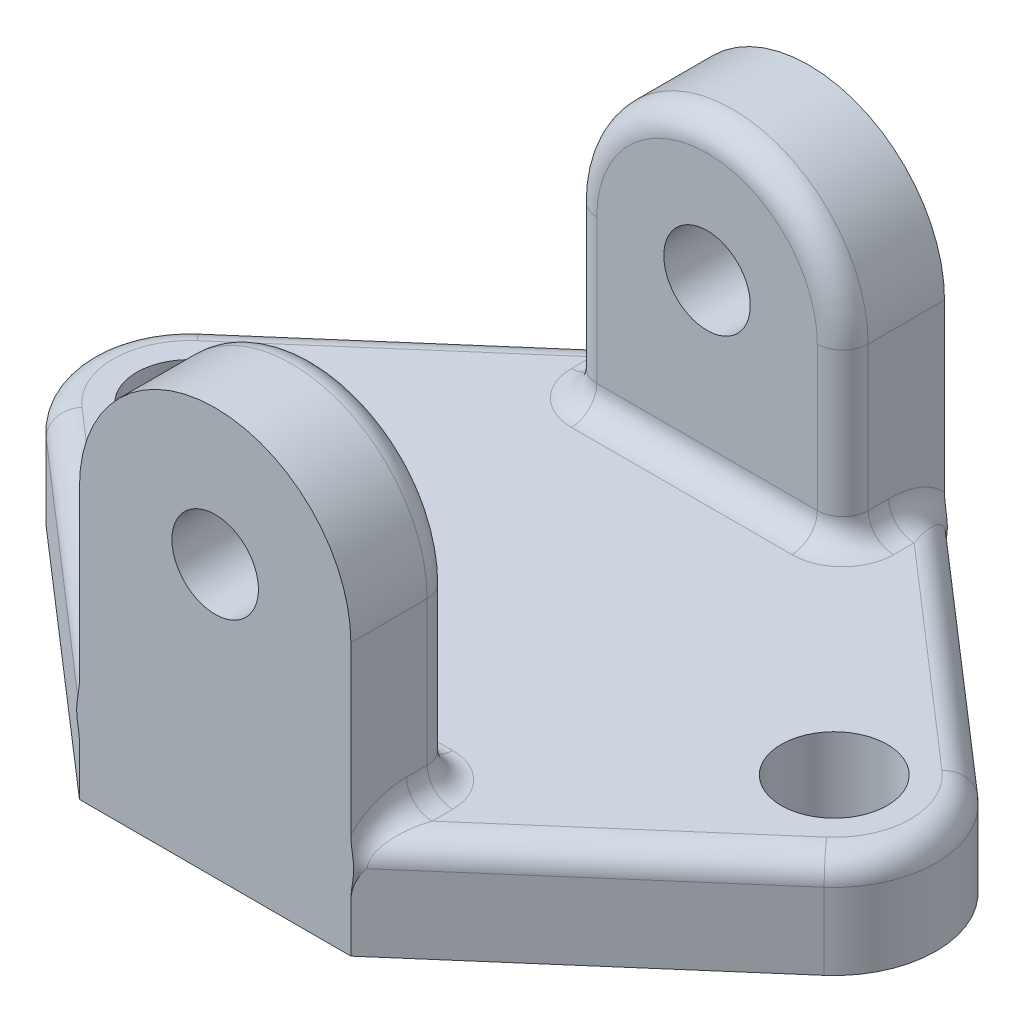
SolidWorks part; units mm, degrees
material "Plain Carbon Steel"
ref_plane "Front" through (0, 0, 0) normal (0, 0, 1) x (1, 0, 0)
ref_plane "Top" through (0, 0, 0) normal (0, 1, 0) x (1, 0, 0)
ref_plane "Right" through (0, 0, 0) normal (1, 0, 0) x (0, 0, -1)
sketch "Sketch1" plane through (0, 0, 0) normal (0, 1, 0) x (1, 0, 0)
  line L0 (0, 44.7996) -> (0, -49.8042) construction
  line L1 (-62.4772, 0) -> (76.0382, 0) construction
  line L2 (-16, 35) -> (16, 35)
  line L3 (16, 35) -> (45.8685, 9.0602)
  line L4 (-16, 35) -> (-45.8685, 9.0602)
  line L5 (50, 0) -> (-50, 0)
  arc A0 (45.8685, 9.0602) -> (50, 0) centre (38, 0) cw
  arc A1 (-45.8685, 9.0602) -> (-50, 0) centre (-38, 0) ccw
  point P8 (0, 35)
  point P12 (0, 0)
  dimension "D3" = 12
  dimension "D4" = 70
  dimension "D1" = 32
  dimension "D2" = 76
extrude "Boss-Extrude1" add sketch "Sketch1" along normal blind 12
sketch "Sketch2" plane through (0, 0, -35) normal (0, 0, -1) x (-1, 0, 0)
  line L0 (-16, 12) -> (-16, 32)
  line L1 (-16, 12) -> (16, 12)
  line L2 (16, 12) -> (16, 32)
  arc A0 (16, 32) -> (-16, 32) centre (0, 32) ccw
  dimension "D1" = 32
extrude "Boss-Extrude2" add sketch "Sketch2" against normal blind 12
hole_wizard "M12x1.75 Tapped Hole1" positions "Sketch4" profile "Sketch5" tap size "M12x1.75" standard "ANSI Metric" end condition up to next
sketch "Sketch4" plane through (0, 0, -35) normal (0, 0, -1) x (-1, 0, 0)
  point P0 (0, 32)
sketch "Sketch5" plane through (0, 32, -35) normal (1, 0, 0) x (0, 1, 0)
  line L0 (0, 0) -> (0, 12)
  line L1 (0, 12) -> (5.1, 12)
  line L2 (5.1, 12) -> (5.1, 0)
  line L5 (5.1, 0) -> (0, 0)
  line L11 (0, -6.35) -> (0, 107.95) construction
  dimension "Thru Tap Drill Dia." = 10.2
  dimension "Thru Tap Drill Depth" = 12
cosmetic thread "Hole Thread1" parameters "D2"=12
fillet "Fillet1" radius 3 4 edges at (-48.9184, 12, -4.9789) (-30.9342, 12, -22.0301) (30.9342, 12, -22.0301) (48.9184, 12, -4.9789)
fillet "Fillet2" radius 3 8 edges at (16, 22, -23) (0, 48, -23) (-16, 11.1213, -33.8362) (16, 11.1213, -33.8362) (-16, 22, -23) (-16, 12, -27.0133) (0, 12, -23) (16, 12, -27.0133)
mirror "Mirror1" about plane through (0, 0, 0) normal (0, 0, 1) of bodies 103
sketch "Sketch7" plane through (0, 12, 0) normal (0, 1, 0) x (1, 0, 0)
  line L0 (-62.0782, 0) -> (58.3871, 0) construction
  circle A0 centre (38, 0) radius 6.25
  circle A1 centre (-38, 0) radius 6.25
  dimension "D1" = 12.5
  dimension "D2" = 76
extrude "Cut-Extrude1" cut sketch "Sketch7" against normal through all
